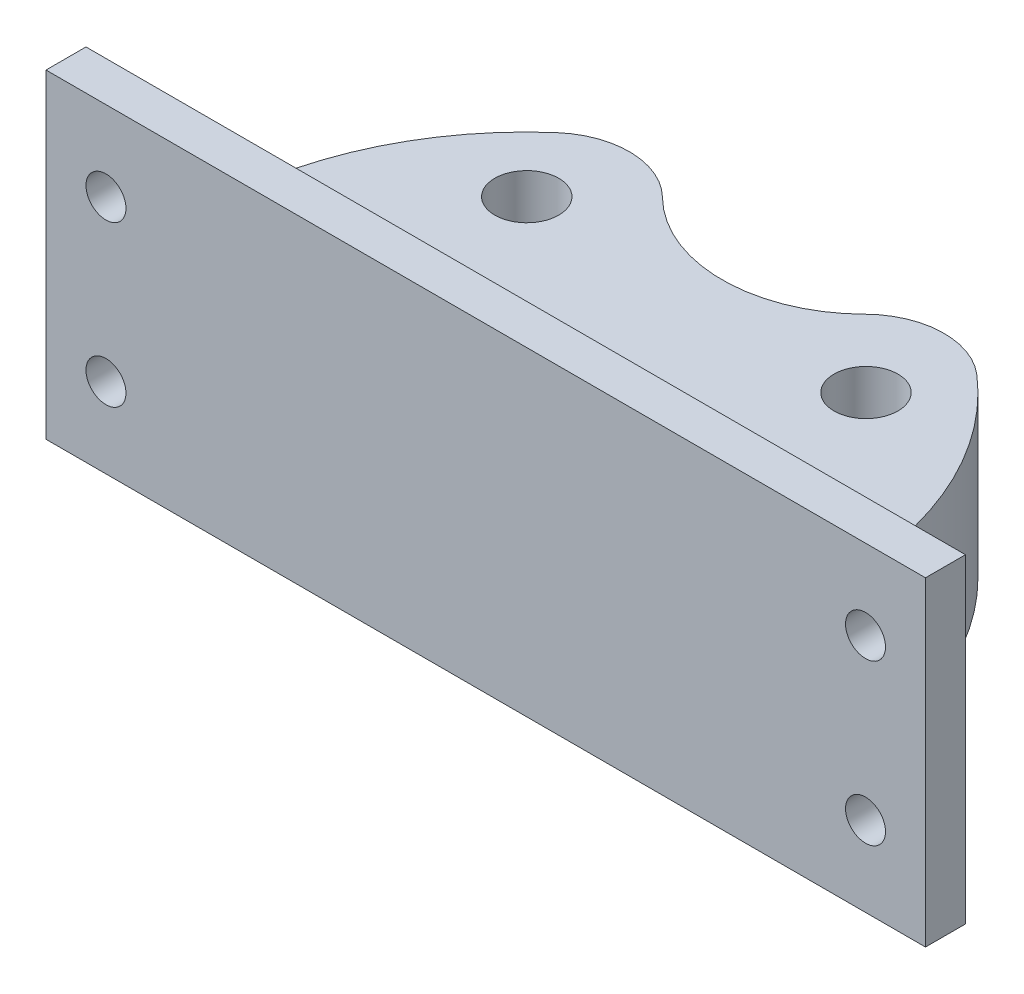
SolidWorks part; units mm, degrees
ref_plane "Front Plane" through (0, 0, 0) normal (0, 0, 1) x (1, 0, 0)
ref_plane "Top Plane" through (0, 0, 0) normal (0, 1, 0) x (1, 0, 0)
ref_plane "Right Plane" through (0, 0, 0) normal (1, 0, 0) x (0, 0, -1)
sketch "Sketch1" plane through (0, 0, 0) normal (0, 1, 0) x (1, 0, 0)
  line L0 (-55, -42.5568) -> (-40, -42.5568)
  line L1 (0, 44.4418) -> (0, -55.9757) construction
  line L4 (-55, -42.5568) -> (-55, -47.5568)
  line L5 (-55, -47.5568) -> (55, -47.5568)
  line L6 (55, -47.5568) -> (55, -42.5568)
  line L7 (40, -42.5568) -> (55, -42.5568)
  line L8 (0, 0) -> (-26.7715, -26.7715) construction
  arc A2 (-16.8665, -6.2867) -> (16.8665, -6.2867) centre (0, 0) ccw
  circle A3 centre (-21.2132, -21.2132) radius 4
  circle A4 centre (21.2132, -21.2132) radius 4
  arc A5 (40, -42.5568) -> (16.8665, -6.2867) centre (0, -42.5568) ccw
  arc A6 (-16.8665, -6.2867) -> (-40, -42.5568) centre (0, -42.5568) ccw
  arc A7 (0, -2.5568) -> (-2.6443, -2.6443) centre (0, -42.5568) ccw
  point P9 (0, -47.5568)
  dimension "D1" = 15
  dimension "D2" = 36
  dimension "D6" = 8
  dimension "D3" = 110
  dimension "D4" = 5
  dimension "D5" = 45
  dimension "D7" = 30
extrude "Boss-Extrude1" add sketch "Sketch1" along normal blind 20 contours A2 A6 L0 L4 L5 L6 L7 A5 A4 A3 region at (0, 0, 32.1663)
sketch "Sketch2" plane through (0, 20, 0) normal (0, 1, 0) x (1, 0, 0)
  line L0 (-55, -42.5568) -> (-55, -47.5568)
  line L1 (-55, -47.5568) -> (55, -47.5568)
  line L2 (55, -47.5568) -> (55, -42.5568)
  line L3 (55, -42.5568) -> (-55, -42.5568)
extrude "Boss-Extrude2" add sketch "Sketch2" along normal blind 10
sketch "Sketch3" plane through (0, 0, 0) normal (0, -1, 0) x (1, 0, 0)
  line L0 (-55, 47.5568) -> (-55, 42.5568)
  line L1 (-55, 42.5568) -> (55, 42.5568)
  line L2 (55, 42.5568) -> (55, 47.5568)
  line L3 (55, 47.5568) -> (-55, 47.5568)
extrude "Boss-Extrude3" add sketch "Sketch3" along normal blind 10
sketch "Sketch4" plane through (0, 0, 47.5568) normal (0, 0, 1) x (1, 0, 0)
  line L0 (-55, 10) -> (55, 10) construction
  line L1 (-55, 30) -> (-55, -10) construction
  line L2 (55, 30) -> (55, -10) construction
  line L3 (-55, 30) -> (55, 30) construction
  line L4 (0, 30) -> (0, -10) construction
  line L5 (55, -10) -> (-55, -10) construction
  circle A0 centre (-47.5, 20) radius 2.5
  circle A1 centre (47.5, 20) radius 2.5
  circle A2 centre (47.5, 0) radius 2.5
  circle A3 centre (-47.5, 0) radius 2.5
  dimension "D1" = 5
  dimension "D2" = 7.5
  dimension "D3" = 10
extrude "Cut-Extrude1" cut sketch "Sketch4" against normal through all
fillet "Fillet1" radius 10 4 edges at (40, 10, 42.5568) (0, 20, 42.5568) (-40, 10, 42.5568) (0, 0, 42.5568)
fillet "Fillet2" radius 10 2 edges at (16.8665, 10, 6.2867) (-16.8665, 10, 6.2867)
